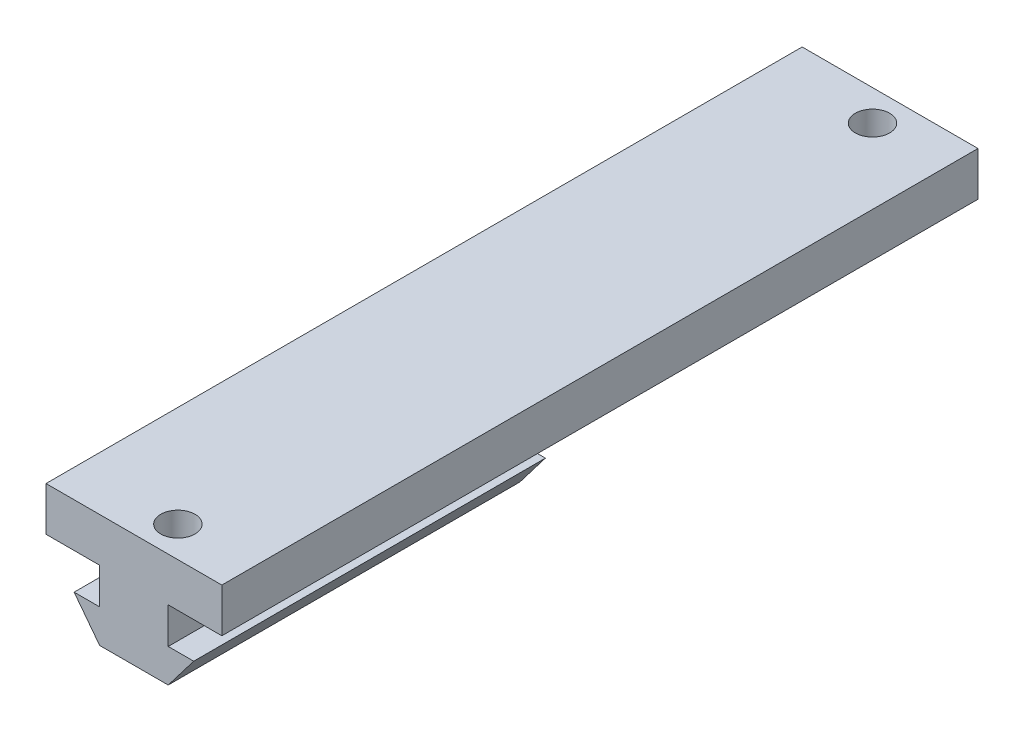
SolidWorks part; units mm, degrees
ref_plane "Front Plane" through (0, 0, 0) normal (0, 0, 1) x (1, 0, 0)
ref_plane "Top Plane" through (0, 0, 0) normal (0, 1, 0) x (1, 0, 0)
ref_plane "Right Plane" through (0, 0, 0) normal (1, 0, 0) x (0, 0, -1)
sketch "Sketch1" plane through (0, 0, 0) normal (0, 1, 0) x (1, 0, 0)
  line L1 (-10, -43) -> (10, -43)
  line L2 (-10, -43) -> (-10, 43)
  line L3 (-10, 43) -> (10, 43)
  line L4 (10, -43) -> (10, 43)
  line L5 (-10, -43) -> (10, 43) construction
  line L6 (-10, 43) -> (10, -43) construction
  point P0 (0, 0)
  dimension "D1" = 20
  dimension "D2" = 86
extrude "Boss-Extrude1" add sketch "Sketch1" along normal blind 5
sketch "Sketch2" plane through (0, 5, 0) normal (0, 1, 0) x (1, 0, 0)
  line L0 (10, 0) -> (-10, 0) construction
  line L1 (10, -43) -> (10, 43) construction
  line L2 (-10, 43) -> (-10, -43) construction
  circle A0 centre (1.5, -39.5) radius 1.95
  circle A1 centre (1.5, 39.5) radius 1.95
  dimension "D1" = 3.9
  dimension "D2" = 11.5
  dimension "D3" = 79
sketch "Sketch4" plane through (0, 0, 43) normal (0, 0, 1) x (1, 0, 0)
  line L0 (0, 0) -> (0, -2.9) construction
  line L1 (-3.9, 0) -> (-3.9, -4.1)
  line L2 (-10, 0) -> (10, 0) construction
  line L3 (-3.9, -4.1) -> (-6.8, -4.1)
  line L4 (-6.8, -4.1) -> (-3.9, -7.9)
  line L5 (-3.9, -7.9) -> (3.9, -7.9)
  line L6 (3.9, -7.9) -> (6.8, -4.1)
  line L7 (6.8, -4.1) -> (3.9, -4.1)
  line L8 (3.9, -4.1) -> (3.9, 0)
  line L9 (-3.9, 0) -> (3.9, 0)
  line L10 (0, 5) -> (0, -7.9) construction
  line L11 (-10, 5) -> (10, 5) construction
  dimension "D1" = 7.8
  dimension "D2" = 2.9
  dimension "D3" = 4.1
  dimension "D4" = 3.8
extrude "Boss-Extrude4" add sketch "Sketch4" against normal blind 40
extrude "Cut-Extrude1" cut sketch "Sketch2" against normal blind 6
